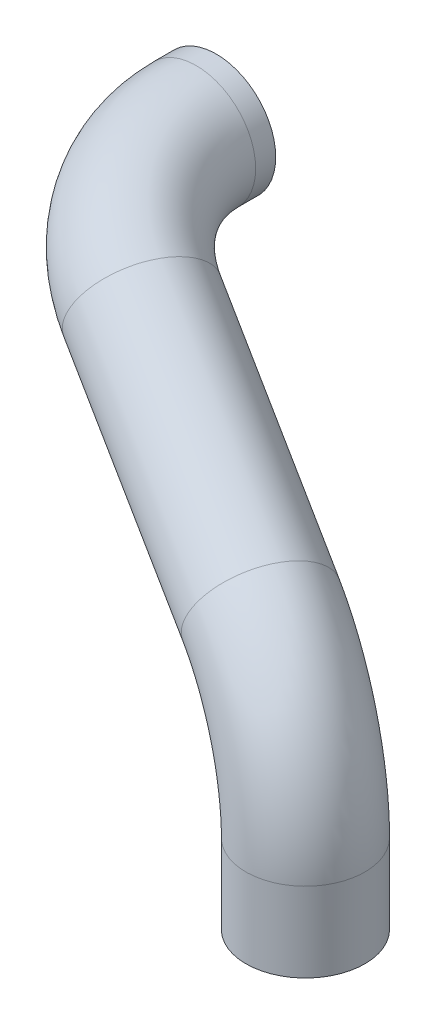
SolidWorks part; units mm, degrees
ref_plane "前视基准面" through (0, 0, 0) normal (0, 0, 1) x (1, 0, 0)
ref_plane "上视基准面" through (0, 0, 0) normal (0, 1, 0) x (1, 0, 0)
ref_plane "右视基准面" through (0, 0, 0) normal (1, 0, 0) x (0, 0, -1)
other "Configuration Table"
sketch3d "3D草图1"
  line L0 (0, 0, 0) -> (0, 13.3701, 0)
  line L1 (-65, 60, -46.6299) -> (-65, 60, -50)
  line L2 (-51.074, 53.5726, -23.5726) -> (-13.926, 36.4274, -6.4274)
  arc A0 (0, 13.3701, 0) -> (-13.926, 36.4274, -6.4274) centre (-22.699, 13.3701, -10.4765) ccw
  arc A1 (-65, 60, -46.6299) -> (-51.074, 53.5726, -23.5726) centre (-42.301, 49.5235, -46.6299) ccw
  point P5 (-55.8188, 60, -27.4533)
  point P9 (0, 30, 0)
  point P10 (-33.1754, 13.3701, 12.2225)
  point P13 (-65, 60, -30)
  point P14 (-31.8246, 72.2225, -46.6299)
  dimension "D6" = 25
  dimension "D1" = 60
  dimension "D2" = 30
  dimension "D3" = 65
  dimension "D4" = 20
  dimension "D5" = 50
sweep "扫描-薄件1" add path "3D草图1" circular profile diameter 20 parameters "D1"=2.5, "D3"=20
